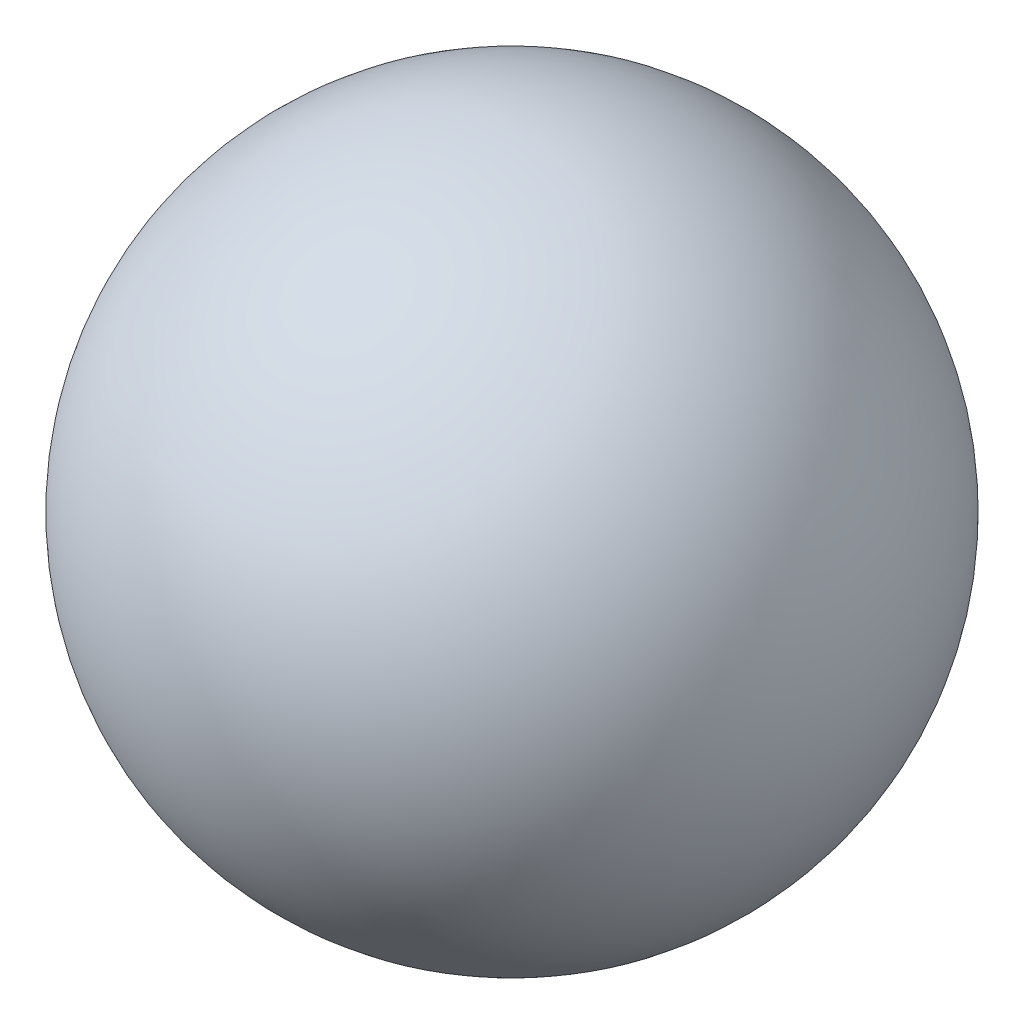
SolidWorks part; units mm, degrees
ref_plane "Front Plane" through (0, 0, 0) normal (0, 0, 1) x (1, 0, 0)
ref_plane "Top Plane" through (0, 0, 0) normal (0, 1, 0) x (1, 0, 0)
ref_plane "Right Plane" through (0, 0, 0) normal (1, 0, 0) x (0, 0, -1)
sketch "Sketch1" plane through (0, 0, 0) normal (0, 0, 1) x (1, 0, 0)
  line L0 (0, 0) -> (0, 10.16) construction
  line L1 (0, 10.16) -> (0, -10.16)
  arc A1 (0, 10.16) -> (0, -10.16) centre (0, 0) ccw
revolve "Revolve3" add sketch "Sketch1" angle 360 about L0
